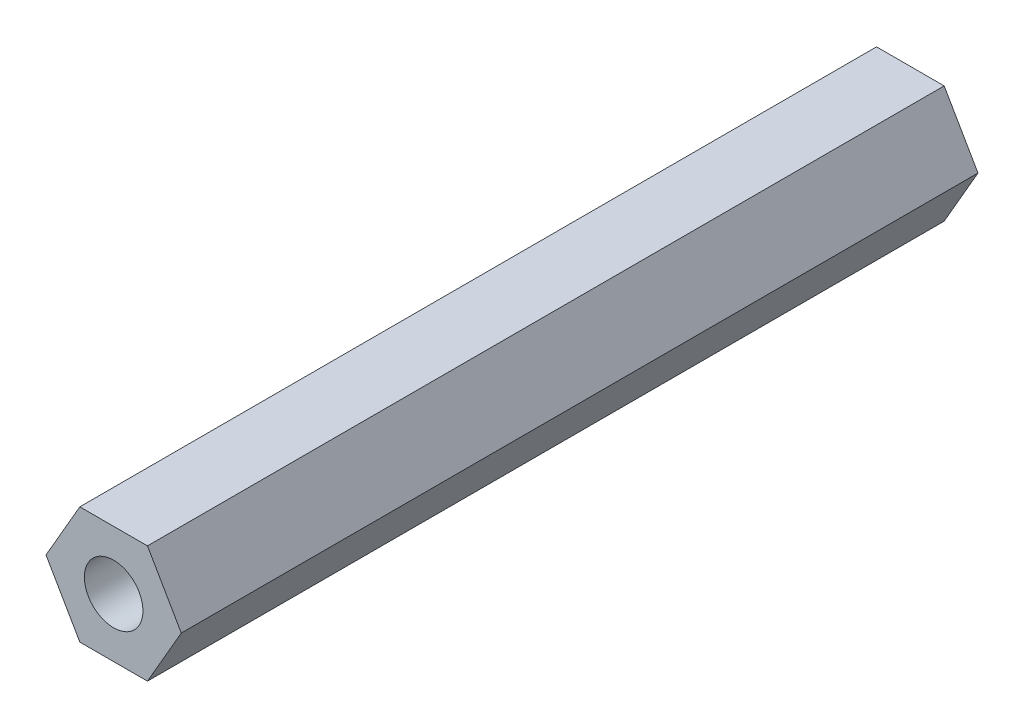
SolidWorks part; units mm, degrees
material "1060 Alloy"
ref_plane "Front Plane" through (0, 0, 0) normal (0, 0, 1) x (1, 0, 0)
ref_plane "Top Plane" through (0, 0, 0) normal (0, 1, 0) x (1, 0, 0)
ref_plane "Right Plane" through (0, 0, 0) normal (1, 0, 0) x (0, 0, -1)
sketch "Sketch1" plane through (0, 0, 0) normal (0, 0, 1) x (1, 0, 0)
  line L1 (3.6662, 6.35) -> (-3.6662, 6.35)
  line L2 (-3.6662, 6.35) -> (-7.3323, 0)
  line L3 (-7.3323, 0) -> (-3.6662, -6.35)
  line L4 (-3.6662, -6.35) -> (3.6662, -6.35)
  line L5 (3.6662, -6.35) -> (7.3323, 0)
  line L6 (7.3323, 0) -> (3.6662, 6.35)
  circle A0 centre (0, 0) radius 6.35 construction
  circle A1 centre (0, 0) radius 3.175
  dimension "D2" = 6.35
  dimension "D1" = 12.7
extrude "Boss-Extrude1" add sketch "Sketch1" along normal mid plane 86.36
